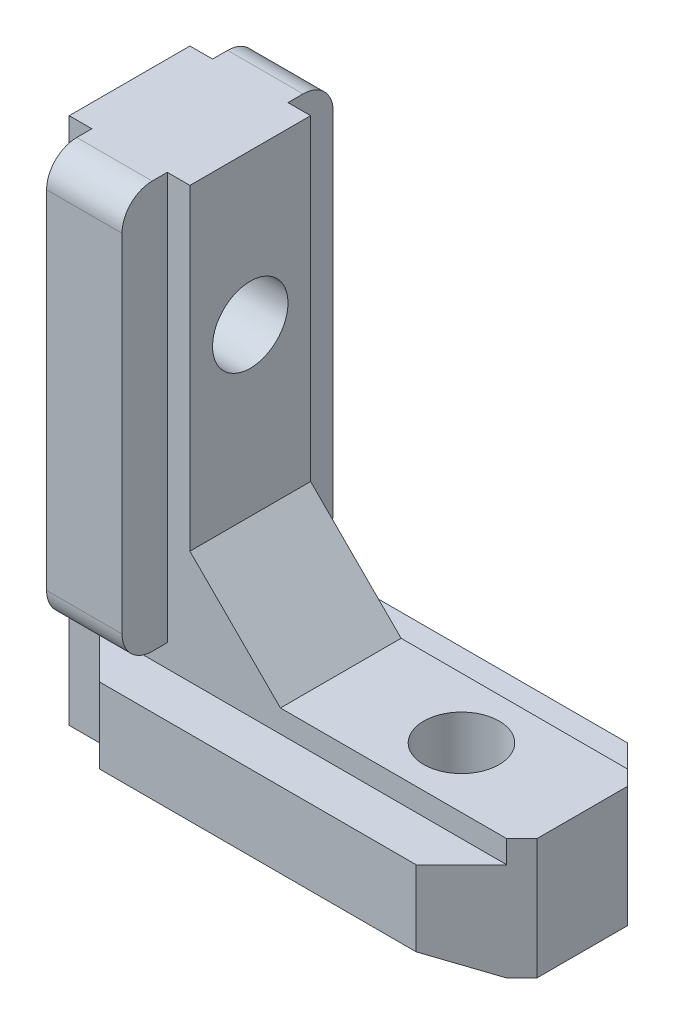
SolidWorks part; units mm, degrees
other "Camera1"
material "Stainless Steel (ferritic)"
ref_plane "Front Plane" through (0, 0, 0) normal (0, 0, 1) x (1, 0, 0)
ref_plane "Top Plane" through (0, 0, 0) normal (0, 1, 0) x (1, 0, 0)
ref_plane "Right Plane" through (0, 0, 0) normal (1, 0, 0) x (0, 0, -1)
sketch "Sketch1" plane through (0, 0, 0) normal (0, 0, 1) x (1, 0, 0)
  line L0 (0, 0) -> (0, 35)
  line L1 (0, 35) -> (8, 35)
  line L2 (8, 35) -> (8, 8)
  line L3 (8, 8) -> (30, 8)
  line L4 (30, 8) -> (30, 0)
  line L5 (30, 0) -> (0, 0)
  dimension "D1" = 8
  dimension "D2" = 8
  dimension "D3" = 30
  dimension "D4" = 35
extrude "Boss-Extrude1" add sketch "Sketch1" along normal mid plane 8
sketch "Sketch2" plane through (30, 0, 0) normal (1, 0, 0) x (0, 0, -1)
  line L0 (-4, 6.5) -> (-7, 6.5)
  line L1 (-4, 0) -> (-4, 8) construction
  line L2 (-7, 6.5) -> (-7, 1.5)
  line L3 (-7, 1.5) -> (-4, 0)
  line L4 (-4, 0) -> (-4, 6.5)
  line L6 (4, 0) -> (4, 6.5)
  line L7 (4, 6.5) -> (7, 6.5)
  line L8 (7, 6.5) -> (7, 1.5)
  line L9 (7, 1.5) -> (4, 0)
  line L11 (-4, 8) -> (4, 8) construction
  dimension "D1" = 1.5
  dimension "D2" = 14
  dimension "D3" = 5
extrude "Boss-Extrude2" add sketch "Sketch2" against normal blind 29
chamfer "Chamfer1" distance 4 angle 45 4 edges at (30, 4, -7) (30, 4, 7) (1, 4, -7) (1, 4, 7)
chamfer "Chamfer2" distance 6 angle 45 1 edges at (8, 8, 0)
sketch "Sketch3" plane through (0, 0, 0) normal (0, -1, 0) x (1, 0, 0)
  line L0 (0, 4) -> (0, -4) construction
  line L1 (0, 0) -> (22.2253, 0) construction
  circle A0 centre (22, 0) radius 2.5
  dimension "D2" = 5
  dimension "D1" = 22
extrude "Cut-Extrude1" cut sketch "Sketch3" against normal up to next
sketch "Sketch4" plane through (0, 0, 0) normal (-1, 0, 0) x (0, 0, 1)
  line L0 (0, 0) -> (0, 35) construction
  line L1 (4, 35) -> (-4, 35) construction
  line L2 (4, 0) -> (-4, 0) construction
  circle A0 centre (0, 25) radius 2.5
  dimension "D1" = 5
  dimension "D2" = 25
extrude "Cut-Extrude2" cut sketch "Sketch4" against normal up to next
sketch "Sketch5" plane through (0, 35, 0) normal (0, 1, 0) x (1, 0, 0)
  line L0 (1.5, 4) -> (1.5, 7)
  line L1 (8, 4) -> (0, 4) construction
  line L2 (1.5, 7) -> (6.5, 7)
  line L3 (6.5, 7) -> (6.5, 4)
  line L4 (2, 4) -> (29, 4) construction
  line L5 (5, 7) -> (26, 7) construction
  line L6 (2, -4) -> (29, -4) construction
  line L7 (6.5, -4) -> (6.5, -7)
  line L8 (6.5, -7) -> (1.5, -7)
  line L9 (1.5, -7) -> (1.5, -4)
  line L10 (8, -4) -> (0, -4) construction
  line L11 (1.5, -4) -> (6.5, -4)
  line L12 (1.5, 4) -> (6.5, 4)
  line L13 (8, -4) -> (8, 4) construction
  dimension "D1" = 1.5
  dimension "D2" = 5
extrude "Boss-Extrude3" add sketch "Sketch5" against normal blind 27
fillet "Fillet1" radius 2 4 edges at (4, 8, -7) (4, 8, 7) (4, 35, -7) (4, 35, 7)
